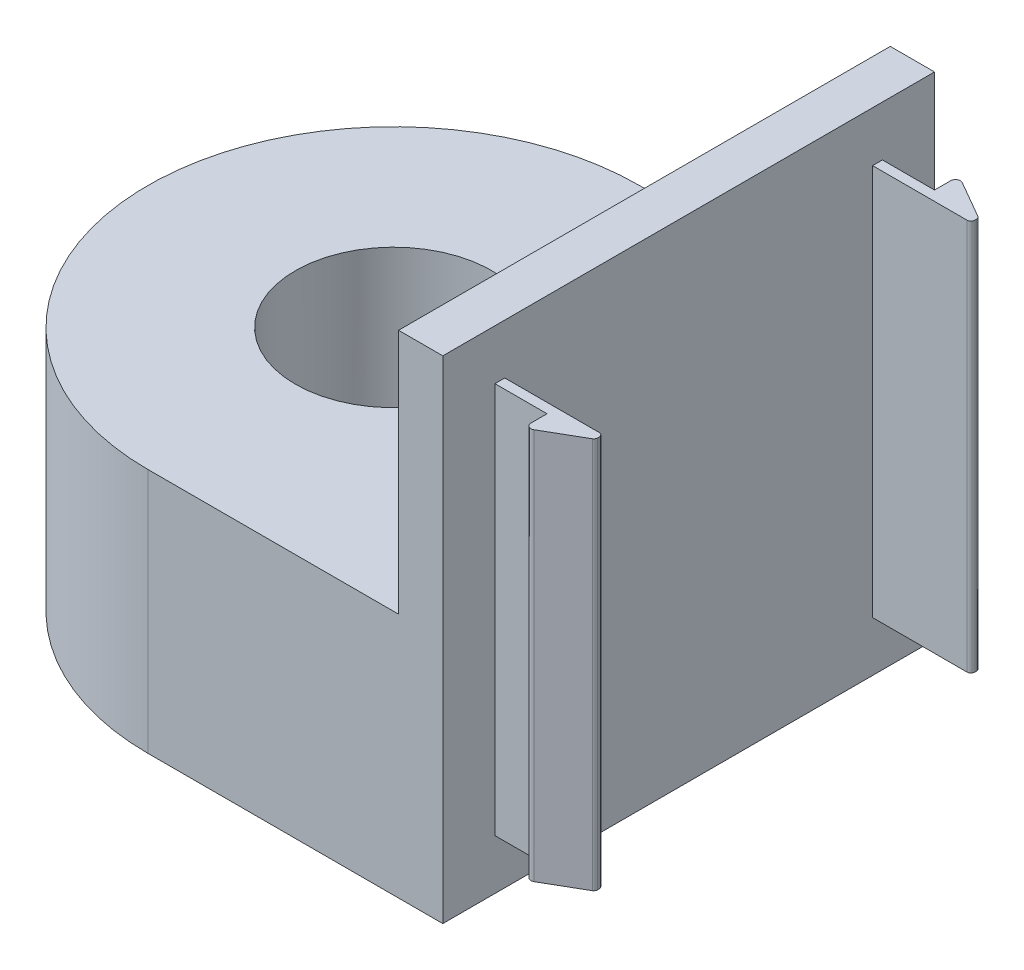
SolidWorks part; units mm, degrees
ref_plane "Front Plane" through (0, 0, 0) normal (0, 0, 1) x (1, 0, 0)
ref_plane "Top Plane" through (0, 0, 0) normal (0, 1, 0) x (1, 0, 0)
ref_plane "Right Plane" through (0, 0, 0) normal (1, 0, 0) x (0, 0, -1)
sketch "Sketch3" plane through (0, 0, 0) normal (0, 1, 0) x (1, 0, 0)
  line L0 (5, 44.7) -> (10.3, 44.7)
  line L1 (0, 0) -> (5, 0)
  line L2 (0, 0) -> (0, 50) construction
  line L3 (0, 50) -> (5, 50)
  line L4 (5, 0) -> (5, 5.3)
  line L5 (0, 50) -> (-25, 50)
  line L6 (0, 50) -> (0, 0) construction
  line L7 (0, 0) -> (-25, 0)
  line L8 (-25, 50) -> (-25, 0) construction
  line L9 (10.3, 44.7) -> (10.3, 47.2)
  line L10 (10.3, 47.2) -> (15, 44.4865)
  line L12 (15, 44.4865) -> (15, 43.7)
  line L13 (15, 43.7) -> (5, 43.7)
  line L14 (5, 6.3) -> (15, 6.3)
  line L15 (15, 6.3) -> (15, 5.5135)
  line L16 (15, 5.5135) -> (10.3, 2.8)
  line L17 (10.3, 2.8) -> (10.3, 5.3)
  line L18 (10.3, 5.3) -> (5, 5.3)
  line L19 (5, 44.7) -> (5, 50)
  line L20 (5, 6.3) -> (5, 43.7)
  arc A1 (-25, 50) -> (-25, 0) centre (-25, 25) ccw
  dimension "D1" = 50
  dimension "D2" = 5
  dimension "D3" = 25
  dimension "D4" = 5.3
  dimension "D5" = 1
  dimension "D6" = 60
  dimension "D7" = 2.5
  dimension "D8" = 5.3
  dimension "D9" = 10
  dimension "D10" = 5.3
  dimension "D11" = 1
  dimension "D12" = 10
  dimension "D13" = 5.3
  dimension "D14" = 60
  dimension "D15" = 2.5
extrude "Boss-Extrude2" add sketch "Sketch3" along normal blind 50
sketch "Sketch4" plane through (0, 50, 0) normal (0, 1, 0) x (1, 0, 0)
  line L9 (-25, 0) -> (5, 0) construction
  line L10 (0, 0) -> (-50, 0)
  line L11 (0, 0) -> (0, 50) construction
  line L12 (0, 50) -> (-50, 50)
  line L13 (-50, 0) -> (-50, 50)
  line L14 (0, 50) -> (0.5, 50)
  line L15 (0, 50) -> (0, 0) construction
  line L16 (0, 0) -> (0.5, 0)
  line L17 (0.5, 50) -> (0.5, 0)
  line M9 (-25, 0) -> (5, 0)
  line M11 (5, 50) -> (-25, 50)
  arc M12 (-25, 50) -> (-25, 0) centre (-25, 25) ccw
  dimension "D1" = 50
  dimension "D2" = 50
  dimension "D3" = 0.5
extrude "Cut-Extrude1" cut sketch "Sketch4" against normal blind 25 contours L15 M11 M12 M9 region at (-22.4124, 50, -25)
sketch "Sketch5" plane through (0, 25, 0) normal (0, 1, 0) x (1, 0, 0)
  line L8 (-25, 0) -> (-25, 50) construction
  circle A0 centre (-25, 25) radius 10
  dimension "D1" = 20
  dimension "D2" = 25
sketch "Sketch10" plane through (0, 0, 0) normal (0, -1, 0) x (1, 0, 0)
  circle A0 centre (-25, -25) radius 15
  dimension "D1" = 30
sketch "Sketch17" plane through (5, 0, 0) normal (1, 0, 0) x (0, 0, -1)
  line L27 (0, 44.9) -> (50, 44.9)
  line L28 (0, 0) -> (50, 0)
  line L29 (0, 0) -> (0, 50)
  line L30 (0, 50) -> (50, 50)
  line L31 (50, 0) -> (50, 50)
  line L32 (0, 5.1) -> (50, 5.1)
  line M17 (0, 0) -> (5.3, 0)
  line M19 (5.3, 50) -> (0, 50)
  line M20 (0, 50) -> (0, 0)
  line M29 (5.3, 0) -> (5.3, 50)
  dimension "D1" = 5.1
  dimension "D2" = 5.1
extrude "Cut-Extrude3" cut sketch "Sketch5" against normal through all
extrude "Cut-Extrude4" cut sketch "Sketch10" against normal blind 5
extrude "Cut-Extrude5" cut sketch "Sketch17" along normal through all contours M29 | M20 M29 M19 | M29 | M20 M17 M29 region at (5, 47.45, -2.65) region at (5, 47.45, -27.65) region at (5, 2.55, -2.65) region at (5, 2.55, -27.65)
fillet "Fillet1" radius 0.4 4 edges at (15, 25, -43.7) (15, 25, -44.4865) (15, 25, -6.3) (15, 25, -5.5135)
fillet "Fillet2" radius 0.5 2 edges at (10.3, 25, -47.2) (10.3, 25, -2.8)
